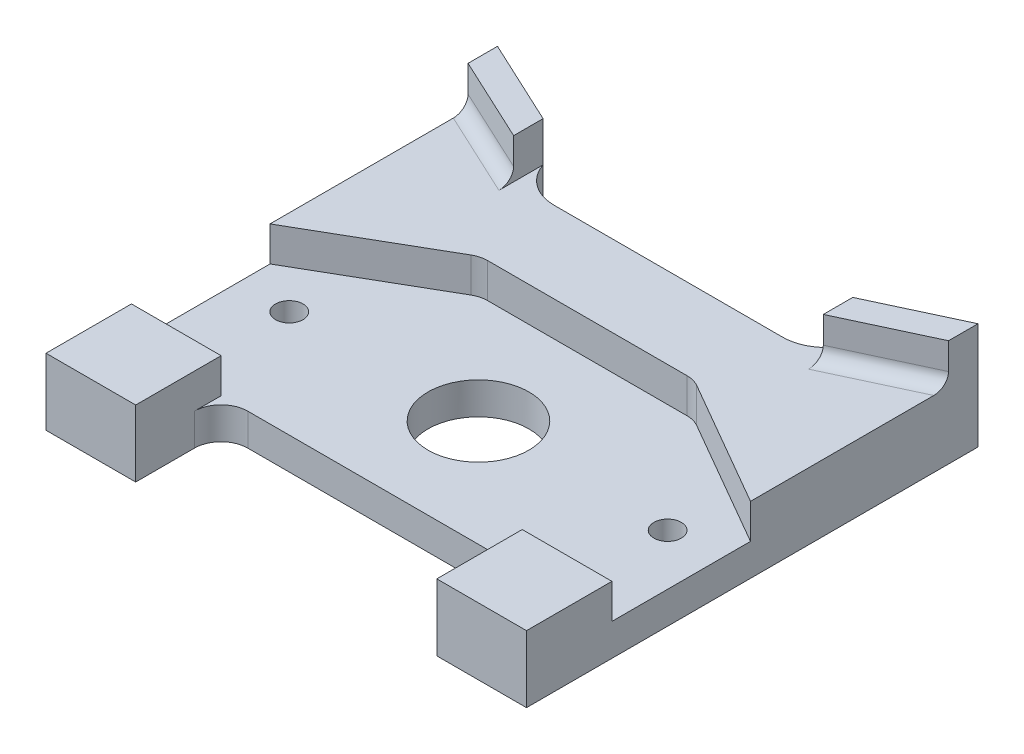
SolidWorks part; units mm, degrees
ref_plane "Front" through (0, 0, 0) normal (0, 0, 1) x (1, 0, 0)
ref_plane "Top" through (0, 0, 0) normal (0, 1, 0) x (1, 0, 0)
ref_plane "Right" through (0, 0, 0) normal (1, 0, 0) x (0, 0, -1)
sketch "Sketch1" plane through (0, 0, 0) normal (0, 1, 0) x (1, 0, 0)
  line L1 (-28.575, -12.7) -> (28.575, -12.7)
  line L2 (-28.575, -12.7) -> (-28.575, 12.7)
  line L3 (-28.575, 12.7) -> (28.575, 12.7)
  line L4 (28.575, -12.7) -> (28.575, 12.7)
  line L5 (-28.575, -12.7) -> (28.575, 12.7) construction
  line L6 (-28.575, 12.7) -> (28.575, -12.7) construction
  point P0 (0, 0)
  dimension "D1" = 57.15
  dimension "D2" = 25.4
extrude "Boss-Extrude1" add sketch "Sketch1" along normal blind 3.81
sketch "Sketch2" plane through (0, 3.81, 0) normal (0, 1, 0) x (1, 0, 0)
  circle A0 centre (0, 0) radius 6
  dimension "D1" = 12
extrude "Cut-Extrude1" cut sketch "Sketch2" against normal up to next
sketch "Sketch3" plane through (0, 3.81, 0) normal (0, 1, 0) x (1, 0, 0)
  line L0 (-50, 0) -> (50, 0) construction
  line L1 (-22.5, 0) -> (22.5, 0) construction
  line L2 (0, -50) -> (0, 50) construction
  point P0 (-22.5, 0)
  point P1 (22.5, 0)
  point P6 (0, 0)
  dimension "D1" = 45
hole_wizard "#4 Clearance Hole1" positions "Sketch4" profile "Sketch6" hole size "#4" standard "ANSI Inch" end condition through all
sketch "Sketch4" plane through (0, 3.81, 0) normal (0, 1, 0) x (1, 0, 0)
  point P0 (-22.5, 0)
  point P3 (22.5, 0)
sketch "Sketch6" plane through (-22.5, 3.81, 0) normal (1, 0, 0) x (0, 0, 1)
  line L0 (0, 0) -> (0, 3.81)
  line L1 (0, 3.81) -> (1.6319, 3.81)
  line L2 (1.6319, 3.81) -> (1.6319, 0)
  line L5 (1.6319, 0) -> (0, 0)
  line L11 (0, -6.35) -> (0, 107.95) construction
  dimension "Thru Hole Dia." = 3.2639
  dimension "Thru Hole Depth" = 3.81
sketch "Sketch7" plane through (0, 3.81, 0) normal (0, 1, 0) x (1, 0, 0)
  line L0 (-46.6907, 21.7722) -> (46.6907, -21.7722) construction
  line L1 (-55.6918, -25.9695) -> (55.6918, 25.9695) construction
  line L2 (-22.5, 0) -> (22.5, 0) construction
  line L3 (-50, 0) -> (50, 0) construction
  dimension "D1" = 25
  dimension "D2" = 25
ref_plane "Plane1" through (0, 12.7, 0) normal (0, 1, 0) x (1, 0, 0)
sketch "Sketch8" plane through (0, 3.81, 0) normal (0, 1, 0) x (1, 0, 0)
  line L1 (-28.575, 12.7) -> (-18.415, 12.7)
  line L10 (28.575, 12.7) -> (-28.575, 12.7) construction
  line L13 (-18.415, 12.7) -> (-18.415, 26.1032)
  line L18 (-29.1631, 27.6119) -> (39.8976, -4.5916) construction
  line L19 (-29.1631, 27.6119) -> (-39.8976, 4.5916) construction
  line L20 (39.8976, -4.5916) -> (29.1631, -27.6119) construction
  line L21 (-39.8976, 4.5916) -> (29.1631, -27.6119) construction
  line L22 (-29.1631, 27.6119) -> (29.1631, -27.6119) construction
  line L23 (39.8976, -4.5916) -> (-39.8976, 4.5916) construction
  line L24 (-181308.2481, 84545.4246) -> (181308.2481, -84545.4246) construction
  line L25 (28.575, -12.7) -> (28.575, -30.8409)
  line L26 (28.575, -30.8409) -> (18.415, -26.1032)
  line L27 (18.415, -26.1032) -> (18.415, -12.7)
  line L28 (-28.575, -12.7) -> (28.575, -12.7) construction
  line L29 (28.575, -12.7) -> (18.415, -12.7)
  line L30 (-18.415, 26.1032) -> (-28.575, 30.8409)
  line L31 (-28.575, 30.8409) -> (-28.575, 12.7)
  point P1 (0, 0)
  line M11 (28.575, 12.7) -> (-28.575, 12.7)
  dimension "D1" = 25.4
  dimension "D2" = 76.2
  dimension "D3" = 10.16
  dimension "D4" = 3.175
  dimension "D5" = 3.175
  dimension "D6" = 10.16
extrude "Boss-Extrude4" add sketch "Sketch8" against normal up to surface (3.81 mm away) contours L30 L31 L13 M11 region at (-23.7493, 3.81, -20.6453) up to plane "Top"
mirror "Mirror4" about plane through (0, 0, 0) normal (1, 0, 0) of "Boss-Extrude4"
mirror "Mirror6" [suppressed] about plane through (0, 0, 0) normal (0, 0, 1)
sketch "Sketch11" plane through (0, 3.81, 0) normal (0, 1, 0) x (1, 0, 0)
  line L6 (-18.415, 26.1032) -> (-28.575, 30.8409)
  line L7 (-28.575, 30.8409) -> (-28.575, 27.3376)
  line L8 (-28.575, 30.8409) -> (-28.575, -12.7) construction
  line L9 (-28.575, 27.3376) -> (-18.415, 22.6)
  line L10 (-18.415, 12.7) -> (-18.415, 26.1032) construction
  line L11 (-18.415, 22.6) -> (-18.415, 26.1032)
  dimension "D1" = 3.175
extrude "Boss-Extrude5" add sketch "Sketch11" along normal up to surface (8.89 mm away) up to plane "Plane1"
mirror "Mirror7" about plane through (0, 0, 0) normal (1, 0, 0) of "Boss-Extrude5"
mirror "Mirror8" [suppressed] about plane through (0, 0, 0) normal (0, 0, 1)
sketch "Sketch12" plane through (0, 3.81, 0) normal (0, 1, 0) x (1, 0, 0)
  line L19 (18.415, 12.7) -> (-18.415, 12.7)
  line L20 (18.415, 12.7) -> (18.415, 22.6)
  line L21 (18.415, 22.6) -> (-18.415, 22.6)
  line L22 (-18.415, 12.7) -> (-18.415, 22.6)
extrude "Boss-Extrude6" add sketch "Sketch12" against normal up to surface (3.81 mm away) up to plane "Top"
sketch "Sketch13" plane through (0, 3.81, 0) normal (0, 1, 0) x (1, 0, 0)
  line L0 (12.7, 12.948) -> (-12.7, 12.948)
  line L1 (-12.7, 12.948) -> (-28.575, 3.7825)
  line L2 (-28.575, 27.3376) -> (-28.575, -12.7) construction
  line L10 (28.575, -12.7) -> (28.575, 27.3376) construction
  line L11 (28.575, 3.7825) -> (12.7, 12.948)
  line L12 (0, -50) -> (0, 50) construction
  line L13 (-28.575, 3.7825) -> (-28.575, 27.3376)
  line L14 (-28.575, 27.3376) -> (-18.415, 22.6)
  line L15 (-18.415, 22.6) -> (18.415, 22.6)
  line L16 (18.415, 22.6) -> (28.575, 27.3376)
  line L17 (28.575, 27.3376) -> (28.575, 3.7825)
  point P15 (0, 12.948)
  dimension "D1" = 9.652
  dimension "D2" = 25.4
  dimension "D3" = 30
  dimension "D4" = 30
extrude "Boss-Extrude7" add sketch "Sketch13" along normal blind 4.1275
fillet "Fillet1" [suppressed] radius 1.5875
fillet "Fillet4" radius 3.175 2 edges at (12.7, 5.8737, -12.948) (-12.7, 5.8737, -12.948)
fillet "Fillet5" radius 1.5875 2 edges at (23.495, 7.9375, -24.9688) (-23.495, 7.9375, -24.9688)
sketch "Sketch14" plane through (0, 0, 0) normal (0, 1, 0) x (1, 0, 0)
  line L1 (28.575, -12.7) -> (17.907, -12.7)
  line L2 (28.575, -12.7) -> (28.575, -22.86)
  line L3 (28.575, -22.86) -> (17.907, -22.86)
  line L4 (17.907, -12.7) -> (17.907, -22.86)
  dimension "D1" = 10.668
  dimension "D2" = 10.16
extrude "Boss-Extrude8" add sketch "Sketch14" along normal up to surface (7.9375 mm away) up to face at (0, 7.9375, -17.079)
mirror "Mirror9" about plane through (0, 0, 0) normal (1, 0, 0) of "Boss-Extrude8"
fillet "Fillet6" radius 3.175 2 edges at (17.907, 1.905, 12.7) (-17.907, 1.905, 12.7)
fillet "Fillet7" radius 5.08 2 edges at (-18.415, 3.9688, -22.6) (18.415, 3.9688, -22.6)
